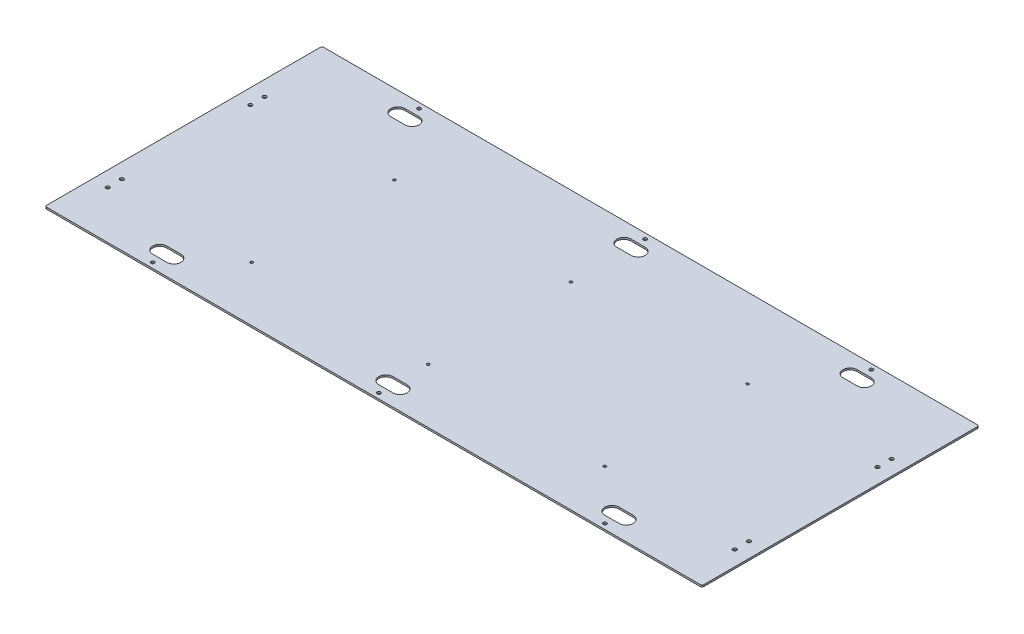
SolidWorks part; units mm, degrees
material "PE High Density"
ref_plane "Front Plane" through (0, 0, 0) normal (0, 0, 1) x (1, 0, 0)
ref_plane "Top Plane" through (0, 0, 0) normal (0, 1, 0) x (1, 0, 0)
ref_plane "Right Plane" through (0, 0, 0) normal (1, 0, 0) x (0, 0, -1)
sketch "Sketch1" plane through (0, 0, 0) normal (0, 1, 0) x (1, 0, 0)
  line L1 (-587.375, -248.92) -> (587.375, -248.92)
  line L2 (-590.55, -245.745) -> (-590.55, 245.745)
  line L3 (-587.375, 248.92) -> (587.375, 248.92)
  line L4 (590.55, -245.745) -> (590.55, 245.745)
  line L5 (-590.55, -248.92) -> (590.55, 248.92) construction
  line L6 (-590.55, 248.92) -> (590.55, -248.92) construction
  arc A0 (587.375, 248.92) -> (590.55, 245.745) centre (587.375, 245.745) cw
  arc A1 (587.375, -248.92) -> (590.55, -245.745) centre (587.375, -245.745) ccw
  arc A2 (-587.375, -248.92) -> (-590.55, -245.745) centre (-587.375, -245.745) cw
  arc A3 (-590.55, 245.745) -> (-587.375, 248.92) centre (-587.375, 245.745) cw
  point P0 (0, 0)
  dimension "D3" = 3.175
  dimension "D1" = 1181.1
  dimension "D2" = 497.84
extrude "Boss-Extrude1" add sketch "Sketch1" along normal blind 3.175
sketch "Sketch2" plane through (0, 3.175, 0) normal (0, 1, 0) x (1, 0, 0)
  line L0 (-590.55, 245.745) -> (-590.55, -245.745) construction
  line L1 (590.55, -245.745) -> (590.55, 245.745) construction
  line L2 (587.375, 248.92) -> (-587.375, 248.92) construction
  line L3 (-587.375, -248.92) -> (587.375, -248.92) construction
  point P0 (-406.4, 239.395)
  point P2 (0, 239.395)
  point P4 (406.4, 239.395)
  point P5 (-406.4, -239.395)
  point P7 (0, -239.395)
  point P9 (406.4, -239.395)
  point P16 (0, 106.045)
  point P17 (-317.5, 106.045)
  point P20 (317.5, 106.045)
  point P21 (-317.5, -150.495)
  point P24 (0, -150.495)
  point P25 (317.5, -150.495)
  point P26 (0, 0)
  point P27 (0, 0)
  point P28 (0, 0)
  point P29 (0, 0)
  point P30 (0, 0)
  point P31 (0, 0)
  point P36 (0, 0)
  point P37 (0, 0)
  point P43 (0, 0)
  point P44 (0, 0)
  point P46 (0, 0)
  dimension "D1" = 184.15
  dimension "D2" = 184.15
  dimension "D3" = 9.525
  dimension "D4" = 9.525
  dimension "D5" = 406.4
  dimension "D6" = 317.5
  dimension "D7" = 317.5
  dimension "D8" = 106.045
  dimension "D9" = 150.495
hole_wizard "1/4 (0.25) Diameter Hole1" positions "Sketch3" profile "Sketch4" hole size "1/4" standard "ANSI Inch" end condition through all
sketch "Sketch3" plane through (0, 3.175, 0) normal (0, 1, 0) x (1, 0, 0)
  point P3 (-406.4, 239.395)
  point P9 (0, 239.395)
  point P15 (406.4, 239.395)
  point P27 (406.4, -239.395)
  point P33 (0, -239.395)
  point P39 (-406.4, -239.395)
sketch "Sketch4" plane through (-406.4, 3.175, -239.395) normal (1, 0, 0) x (0, 0, 1)
  line L0 (0, 0) -> (0, 3.175)
  line L1 (0, 3.175) -> (3.175, 3.175)
  line L2 (3.175, 3.175) -> (3.175, 0)
  line L5 (3.175, 0) -> (0, 0)
  line L11 (0, -6.35) -> (0, 107.95) construction
  dimension "Thru Hole Dia." = 6.35
  dimension "Thru Hole Depth" = 3.175
sketch "Sketch5" plane through (0, 3.175, 0) normal (0, 1, 0) x (1, 0, 0)
  line L0 (-419.1, 213.995) -> (-393.7, 213.995) construction
  line L1 (-419.1, 226.695) -> (-393.7, 226.695)
  line L2 (-419.1, 201.295) -> (-393.7, 201.295)
  line L6 (-12.7, 213.995) -> (12.7, 213.995) construction
  line L7 (-12.7, 226.695) -> (12.7, 226.695)
  line L8 (-12.7, 201.295) -> (12.7, 201.295)
  line L9 (590.55, -245.745) -> (590.55, 245.745) construction
  line L12 (393.7, 213.995) -> (419.1, 213.995) construction
  line L13 (393.7, 226.695) -> (419.1, 226.695)
  line L14 (393.7, 201.295) -> (419.1, 201.295)
  line L15 (-419.1, -213.995) -> (-393.7, -213.995) construction
  line L16 (-419.1, -201.295) -> (-393.7, -201.295)
  line L17 (-419.1, -226.695) -> (-393.7, -226.695)
  line L21 (-12.7, -213.995) -> (12.7, -213.995) construction
  line L22 (-12.7, -201.295) -> (12.7, -201.295)
  line L23 (-12.7, -226.695) -> (12.7, -226.695)
  line L27 (393.7, -213.995) -> (419.1, -213.995) construction
  line L28 (393.7, -201.295) -> (419.1, -201.295)
  line L29 (393.7, -226.695) -> (419.1, -226.695)
  line L31 (-590.55, 245.745) -> (-590.55, -245.745) construction
  arc A0 (-419.1, 226.695) -> (-419.1, 201.295) centre (-419.1, 213.995) ccw
  arc A1 (-393.7, 201.295) -> (-393.7, 226.695) centre (-393.7, 213.995) ccw
  arc A4 (-12.7, 226.695) -> (-12.7, 201.295) centre (-12.7, 213.995) ccw
  arc A5 (12.7, 201.295) -> (12.7, 226.695) centre (12.7, 213.995) ccw
  arc A8 (393.7, 226.695) -> (393.7, 201.295) centre (393.7, 213.995) ccw
  arc A9 (419.1, 201.295) -> (419.1, 226.695) centre (419.1, 213.995) ccw
  arc A10 (-419.1, -201.295) -> (-419.1, -226.695) centre (-419.1, -213.995) ccw
  arc A11 (-393.7, -226.695) -> (-393.7, -201.295) centre (-393.7, -213.995) ccw
  arc A14 (-12.7, -201.295) -> (-12.7, -226.695) centre (-12.7, -213.995) ccw
  arc A15 (12.7, -226.695) -> (12.7, -201.295) centre (12.7, -213.995) ccw
  arc A18 (393.7, -201.295) -> (393.7, -226.695) centre (393.7, -213.995) ccw
  arc A19 (419.1, -226.695) -> (419.1, -201.295) centre (419.1, -213.995) ccw
  circle A20 centre (-406.4, 239.395) radius 3.175 construction
  circle A21 centre (-406.4, -239.395) radius 3.175 construction
  circle A22 centre (0, 239.395) radius 3.175 construction
  circle A23 centre (406.4, 239.395) radius 3.175 construction
  circle A24 centre (406.4, -239.395) radius 3.175 construction
  point P2 (-406.4, 213.995)
  point P16 (0, 213.995)
  point P30 (406.4, 213.995)
  point P37 (-406.4, -213.995)
  point P51 (0, -213.995)
  point P65 (406.4, -213.995)
  dimension "D1" = 12.7
  dimension "D2" = 12.7
  dimension "D11" = 12.7
  dimension "D3" = 25.4
  dimension "D4" = 25.4
  dimension "D5" = 184.15
  dimension "D6" = 406.4
  dimension "D7" = 406.4
  dimension "D8" = 406.4
  dimension "D9" = 406.4
  dimension "D10" = 184.15
  dimension "D12" = 12.7
  dimension "D13" = 12.7
  dimension "D14" = 184.15
extrude "Cut-Extrude1" cut sketch "Sketch5" against normal through all
hole_wizard "#10 (0.1935) Diameter Hole7" positions "3DSketch2" profile "Sketch10" hole size "#10" standard "ANSI Inch" end condition through all
sketch3d "3DSketch2"
  point P0 (-317.5, 3.175, -106.045)
  point P3 (0, 3.175, -106.045)
  point P12 (317.5, 3.175, -106.045)
  point P15 (317.5, 3.175, 150.495)
  point P18 (0, 3.175, 150.495)
  point P27 (-317.5, 3.175, 150.495)
sketch "Sketch10" plane through (-317.5, 3.175, -106.045) normal (1, 0, 0) x (0, 0, 1)
  line L0 (0, 0) -> (0, 3.175)
  line L1 (0, 3.175) -> (2.4574, 3.175)
  line L2 (2.4574, 3.175) -> (2.4574, 0)
  line L5 (2.4574, 0) -> (0, 0)
  line L11 (0, -6.35) -> (0, 107.95) construction
  dimension "Thru Hole Dia." = 4.9149
  dimension "Thru Hole Depth" = 3.175
sketch "Sketch11" plane through (0, 3.175, 0) normal (0, 1, 0) x (1, 0, 0)
  line L0 (-590.55, 245.745) -> (-590.55, -245.745) construction
  line L1 (-563.5625, 118.745) -> (563.5625, 118.745) construction
  line L2 (-563.5625, 118.745) -> (-563.5625, -163.195) construction
  line L3 (-563.5625, -163.195) -> (563.5625, -163.195) construction
  line L4 (563.5625, 118.745) -> (563.5625, -163.195) construction
  line L5 (-563.5625, 118.745) -> (563.5625, -163.195) construction
  line L6 (-563.5625, -163.195) -> (563.5625, 118.745) construction
  line L8 (563.5625, -137.795) -> (-563.5625, -137.795) construction
  line L9 (563.5625, -137.795) -> (563.5625, 93.345) construction
  line L10 (563.5625, 93.345) -> (-563.5625, 93.345) construction
  line L11 (-563.5625, -137.795) -> (-563.5625, 93.345) construction
  line L12 (563.5625, -137.795) -> (-563.5625, 93.345) construction
  line L13 (563.5625, 93.345) -> (-563.5625, -137.795) construction
  point P0 (0, -22.225)
  point P5 (0, 0)
  point P9 (0, -22.225)
  dimension "D1" = 26.9875
  dimension "D2" = 281.94
  dimension "D3" = 25.4
  dimension "D4" = 22.225
hole_wizard "17/64 (0.26563) Diameter Hole1" positions "Sketch12" profile "Sketch13" hole size "17/64" standard "ANSI Inch" end condition up to next
sketch "Sketch12" plane through (0, 3.175, 0) normal (0, 1, 0) x (1, 0, 0)
  point P0 (-563.5625, 118.745)
  point P3 (-563.5625, 93.345)
  point P6 (-563.5625, -137.795)
  point P9 (-563.5625, -163.195)
  point P12 (563.5625, -163.195)
  point P15 (563.5625, -137.795)
  point P18 (563.5625, 118.745)
  point P21 (563.5625, 93.345)
sketch "Sketch13" plane through (-563.5625, 3.175, -118.745) normal (1, 0, 0) x (0, 0, 1)
  line L0 (0, 0) -> (0, 3.175)
  line L1 (0, 3.175) -> (3.3735, 3.175)
  line L2 (3.3735, 3.175) -> (3.3735, 0)
  line L5 (3.3735, 0) -> (0, 0)
  line L11 (0, -6.35) -> (0, 107.95) construction
  dimension "Thru Hole Dia." = 6.747
  dimension "Thru Hole Depth" = 3.175
